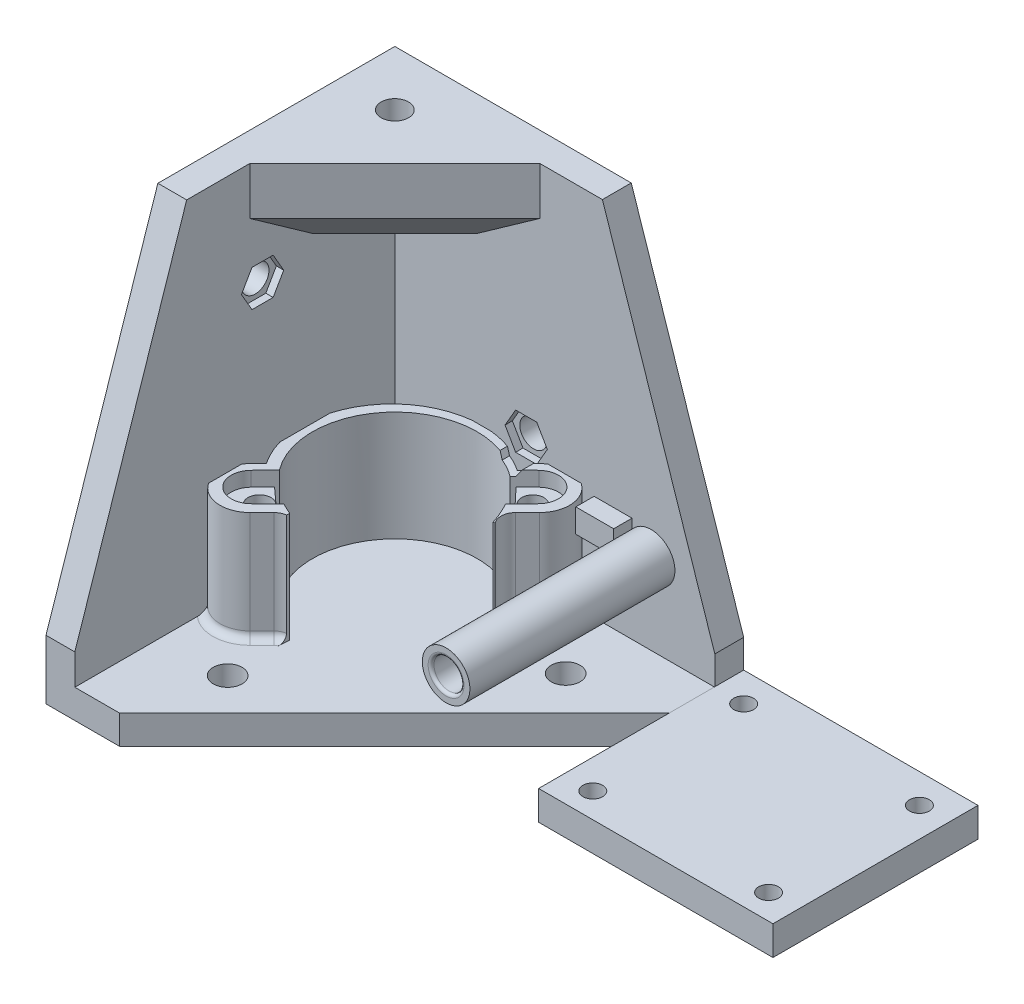
SolidWorks part; units mm, degrees
ref_plane "Front" through (0, 0, 0) normal (0, 0, 1) x (1, 0, 0)
ref_plane "Top" through (0, 0, 0) normal (0, 1, 0) x (1, 0, 0)
ref_plane "Right" through (0, 0, 0) normal (1, 0, 0) x (0, 0, -1)
sketch "Sketch1" plane through (0, 0, 0) normal (0, 1, 0) x (1, 0, 0)
  line L0 (0, 0) -> (0, 60.5)
  line L1 (0, -55) -> (0, 55) construction
  line L2 (0, 60.5) -> (60.5, 60.5)
  line L3 (60.5, 60.5) -> (60.5, 47.75)
  line L4 (60.5, 47.75) -> (12.75, 0)
  line L5 (-55, 0) -> (55, 0) construction
  line L6 (12.75, 0) -> (0, 0)
  dimension "D1" = 60.5
  dimension "D2" = 12.75
extrude "Boss-Extrude1" add sketch "Sketch1" along normal blind 5
sketch "Sketch4" plane through (0, 0, 0) normal (-1, 0, 0) x (0, 0, 1)
  line L0 (-60.5, 5) -> (-60.5, 68.5)
  line L1 (-60.5, 68.5) -> (-19.4, 68.5)
  line L2 (-19.4, 68.5) -> (0, 10.3086)
  line L3 (0, 10.3086) -> (0, 5)
  line L4 (0, -2.75) -> (0, 2.75) construction
  line L5 (-60.5, 5) -> (0, 5) construction
  line L6 (-60.5, 5) -> (0, 5)
  dimension "D1" = 63.5
  dimension "D2" = 41.1
  dimension "D3" = 61.34
extrude "Boss-Extrude2" add sketch "Sketch4" against normal blind 5
sketch "Sketch5" plane through (0, 0, -60.5) normal (0, 0, -1) x (-1, 0, 0)
  line L0 (0, 68.5) -> (-41, 68.5)
  line L1 (-41, 68.5) -> (-60.5, 10.0047)
  line L2 (-60.5, 10.0047) -> (-60.5, 5)
  line L6 (-60.5, 0) -> (0, 0)
  line L7 (0, 0) -> (0, 68.5)
  line L8 (0, 68.5) -> (-5, 68.5)
  line L9 (-5, 68.5) -> (-5, 5)
  line L10 (-5, 5) -> (-60.5, 5)
  line L11 (-60.5, 5) -> (-60.5, 0)
  line L12 (-60.5, 0) -> (0, 0)
  line L13 (0, 0) -> (0, 68.5)
  line L14 (0, 68.5) -> (-5, 68.5)
  line L15 (-5, 68.5) -> (-5, 5)
  line L16 (-5, 5) -> (-60.5, 5)
  line L17 (-60.5, 5) -> (-60.5, 0)
  line M13 (-5, 68.5) -> (-5, 5)
  line M14 (-5, 5) -> (-60.5, 5)
  dimension "D2" = 41
  dimension "D3" = 61.66
  dimension "D1" = 0
extrude "Boss-Extrude3" add sketch "Sketch5" against normal blind 5 contours L1 L2 L0 M14 M13 region at (28.6471, 34.3845, -60.5)
sketch "Sketch6" plane through (0, 5, 0) normal (0, 1, 0) x (1, 0, 0)
  line L0 (60.5, 60.5) -> (0, 60.5) construction
  line L4 (0, 19.4) -> (0, 0)
  line L5 (60.5, 55.5) -> (5, 55.5)
  line L6 (5, 55.5) -> (5, 0)
  line L7 (5, 0) -> (12.75, 0)
  line L8 (12.75, 0) -> (60.5, 47.75)
  line L9 (60.5, 47.75) -> (60.5, 55.5)
  line L10 (60.5, 55.5) -> (5, 55.5)
  line L11 (5, 55.5) -> (5, 0)
  line L12 (5, 0) -> (12.75, 0)
  line L13 (12.75, 0) -> (60.5, 47.75)
  line L14 (60.5, 47.75) -> (60.5, 55.5)
  line L15 (0, 0) -> (5, 0)
  line L16 (5, 0) -> (5, 19.4)
  line L17 (5, 19.4) -> (0, 19.4)
  line L18 (0, 19.4) -> (0, 0)
  line L19 (0, 0) -> (5, 0)
  line L20 (5, 0) -> (5, 19.4)
  line L21 (5, 19.4) -> (0, 19.4)
  line L24 (0, 60.5) -> (0, 19.4)
  line L25 (0, 19.4) -> (5, 19.4)
  line L26 (5, 19.4) -> (5, 55.5)
  line L27 (5, 55.5) -> (41, 55.5)
  line L28 (41, 55.5) -> (41, 60.5)
  line L29 (41, 60.5) -> (0, 60.5)
  line L30 (0, 60.5) -> (0, 19.4)
  line L31 (0, 19.4) -> (5, 19.4)
  line L32 (5, 19.4) -> (5, 55.5)
  line L33 (5, 55.5) -> (41, 55.5)
  line L34 (41, 55.5) -> (41, 60.5)
  line L35 (41, 60.5) -> (0, 60.5)
  circle A0 centre (16.5, 15) radius 2.5
  circle A1 centre (45.5, 44.625) radius 2.5
  dimension "D1" = 5
  dimension "D2" = 5
  dimension "D3" = 0
  dimension "D4" = 15
  dimension "D6" = 16.5
  dimension "D7" = 15
  dimension "D9" = 15.875
  dimension "D5" = 0
  dimension "D8" = 0
extrude "Cut-Extrude1" cut sketch "Sketch6" against normal through all contours A0 | A1 region at (16.5, 5, -15) region at (45.5, 5, -44.625)
sketch "Sketch9" plane through (0, 0, -55.5) normal (0, 0, 1) x (1, 0, 0)
  line L1 (5, 68.5) -> (5, 5) construction
  line L5 (0, 0) -> (60.5, 0)
  line L6 (0, 68.5) -> (0, 0)
  line L7 (41, 68.5) -> (0, 68.5)
  line L8 (60.5, 10.0047) -> (41, 68.5)
  line L9 (60.5, 0) -> (60.5, 10.0047)
  line L10 (0, 0) -> (60.5, 0)
  line L11 (0, 68.5) -> (0, 0)
  line L12 (41, 68.5) -> (0, 68.5)
  line L13 (60.5, 10.0047) -> (41, 68.5)
  line L14 (60.5, 0) -> (60.5, 10.0047)
  line L15 (49.45, 19.0462) -> (49.45, 11.3161) construction
  circle A0 centre (49.45, 19.0462) radius 4.1275
  circle A1 centre (49.45, 19.0462) radius 2.6035
  dimension "D2" = 5.207
  dimension "D3" = 1.524
  dimension "D4" = 49.4538
  dimension "D5" = 44.45
  dimension "D1" = 0
extrude "Boss-Extrude5" add sketch "Sketch9" along normal blind 35.56 contours A1 A0 region at (45.4392, 19.0462, -55.5)
fillet "Fillet1" radius 0.508 1 edges at (52.0535, 19.0462, -19.94)
sketch "Sketch14" plane through (0, 5, 0) normal (0, 1, 0) x (1, 0, 0)
  line L0 (13.4627, 27.5396) -> (14.7681, 26.7924)
  line L1 (12.75, 0) -> (60.5, 47.75) construction
  line L2 (36.625, 23.875) -> (5, 55.5) construction
  line L3 (5, 55.5) -> (60.5, 55.5) construction
  line L4 (32.9604, 47.0373) -> (33.7076, 45.7319)
  line L5 (14.8281, 26.8523) -> (11.8274, 23.8516)
  line L6 (6.723, 28.8027) -> (9.1327, 31.3641)
  line L7 (33.6477, 45.6719) -> (36.6484, 48.6726)
  line L8 (31.6973, 53.777) -> (29.1359, 51.3673)
  line L9 (15.0744, 24.4582) -> (13.006, 22.3898)
  line L10 (5.6561, 29.7396) -> (7.0609, 31.1444)
  line L11 (36.0418, 45.4256) -> (38.1102, 47.494)
  line L12 (30.7604, 54.8439) -> (28.83, 52.9135)
  line L13 (18.1324, 24.8665) -> (30.5234, 17.7734)
  line L14 (35.6335, 42.3676) -> (42.7266, 29.9766)
  line L15 (31.7409, 18.9909) -> (18.852, 25.7543)
  line L16 (41.5091, 28.7591) -> (34.7457, 41.648)
  line L17 (16.5689, 25.6946) -> (16.5343, 25.1798)
  line L18 (34.7457, 41.648) -> (35.7996, 42.0774)
  circle A0 centre (20.5607, 39.9393) radius 14.2875
  arc A1 (11.8274, 23.8516) -> (6.723, 28.8027) centre (9.3129, 26.3661) cw
  arc A2 (36.6484, 48.6726) -> (31.6973, 53.777) centre (34.1339, 51.1871) ccw
  arc A3 (13.006, 22.3898) -> (5.6561, 29.7396) centre (9.3311, 26.0647) cw
  arc A4 (38.1102, 47.494) -> (30.7604, 54.8439) centre (34.4353, 51.1689) ccw
  arc A5 (7.0609, 31.1444) -> (28.83, 52.9135) centre (20.0709, 39.9035) cw
  arc A6 (36.0418, 45.4256) -> (35.6335, 42.3676) centre (37.8378, 43.6295) ccw
  arc A7 (15.0744, 24.4582) -> (18.1324, 24.8665) centre (16.8705, 22.6622) cw
  arc A9 (33.8602, 45.8844) -> (36.3595, 38.5726) centre (13.6025, 34.877) cw
  arc A10 (14.6156, 26.6398) -> (21.9274, 24.1405) centre (25.623, 46.8975) ccw
  point P40 (34.6689, 44.0527)
  point P43 (16.4473, 25.8311)
  line M13 (60.5, 55.5) -> (5, 55.5)
  line M14 (5, 55.5) -> (5, 0)
  line M16 (12.75, 0) -> (60.5, 47.75)
  dimension "D1" = 28.575
  dimension "D2" = 3.556
  dimension "D3" = 2.54
extrude "Boss-Extrude6" add sketch "Sketch14" along normal blind 19.05 contours L2 A0 L5 A1 L6 A5 L10 A3 L9 A7 L13 M16 M14 | L2 L14 A6 L11 A4 L12 A5 A0 L8 A2 L7 M16 M13 region at (7.691, 5, -30.3062) region at (10.0875, 5, -50.8829)
sketch "Sketch15" plane through (0, 68.5, 0) normal (0, 1, 0) x (1, 0, 0)
  line L0 (5, 30.3375) -> (30.1625, 55.5)
  line L1 (0, -33.275) -> (0, 33.275) construction
  line L2 (41, 60.5) -> (0, 60.5) construction
  line L6 (0, 60.5) -> (0, 19.4)
  line L7 (0, 19.4) -> (5, 19.4)
  line L8 (5, 19.4) -> (5, 55.5)
  line L9 (5, 55.5) -> (41, 55.5)
  line L10 (41, 55.5) -> (41, 60.5)
  line L11 (41, 60.5) -> (0, 60.5)
  line L13 (0, 19.4) -> (5, 19.4)
  line L14 (5, 30.3375) -> (5, 55.5)
  line L15 (5, 55.5) -> (30.1625, 55.5)
  line L16 (41, 55.5) -> (41, 60.5)
  circle A0 centre (9.525, 50.975) radius 2.3812
  line M11 (5, 19.4) -> (5, 55.5)
  line M12 (5, 55.5) -> (41, 55.5)
  dimension "D3" = 4.7625
  dimension "D4" = 9.525
  dimension "D5" = 9.525
  dimension "D2" = 45
  dimension "D1" = 0
extrude "Boss-Extrude7" add sketch "Sketch15" against normal blind 15.875 contours L0 A0 M11 M12 region at (13.6178, 68.5, -46.8822)
chamfer "Chamfer2" distance 7.62 angle 45 1 edges at (17.5813, 52.625, -42.9187)
fillet "Fillet2" radius 1.27 7 edges at (39.6065, 5, -51.6871) (37.076, 5, -46.4598) (35.3202, 5, -43.9657) (8.8129, 5, -20.8935) (14.0402, 5, -23.424) (15.745, 5, -24.9392) (35.7165, 5, -42.2225)
sketch "Sketch16" plane through (0, 0, -55.5) normal (0, 0, 1) x (1, 0, 0)
  line L1 (46.1305, 23.2107) -> (38.2864, 23.2107)
  line L2 (46.1305, 23.2107) -> (46.1305, 19.0978)
  line L3 (46.1305, 19.0978) -> (38.2864, 19.0978)
  line L4 (38.2864, 23.2107) -> (38.2864, 19.0978)
extrude "Boss-Extrude8" add sketch "Sketch16" along normal blind 3.175
chamfer "Chamfer3" distance 1.27 angle 45 1 edges at (38.2864, 23.2107, -55.0794)
sketch "Sketch17" plane through (0, 5, 0) normal (0, 1, 0) x (1, 0, 0)
  line L0 (8.716, 30.9212) -> (14.047, 26.0712)
  line L1 (36.625, 23.875) -> (5, 55.5) construction
  line L2 (12.75, 0) -> (60.5, 47.75) construction
  line L3 (5, 55.5) -> (18.418, 55.5) construction
  line L4 (5, 55.5) -> (5, 44.2452) construction
  line L5 (29.6632, 51.8634) -> (34.5959, 46.6202)
  line L22 (37.3079, 55.5) -> (31.5627, 55.5)
  line L23 (30.7604, 54.8439) -> (28.83, 52.9135)
  line L24 (21.7238, 55.5) -> (18.418, 55.5)
  line L25 (5, 44.2452) -> (5, 35.5618)
  line L26 (7.0609, 31.1444) -> (5.6561, 29.7396)
  line L27 (5, 28.9373) -> (5, 23.1921)
  line L28 (13.006, 22.3898) -> (15.0744, 24.4582)
  line L29 (16.5343, 25.1798) -> (16.5689, 25.6946)
  line L30 (16.5343, 25.1798) -> (16.5689, 25.6946)
  line L31 (35.539, 41.9712) -> (35.7996, 42.0774)
  line L32 (35.539, 41.9712) -> (35.7996, 42.0774)
  line L33 (14.6156, 26.6398) -> (11.8274, 23.8516)
  line L34 (6.723, 28.8027) -> (9.1327, 31.3641)
  line L35 (29.1359, 51.3673) -> (31.6973, 53.777)
  line L36 (36.6484, 48.6726) -> (33.8602, 45.8844)
  line L40 (35.7996, 42.0774) -> (35.6335, 42.3676)
  line L41 (36.0418, 45.4256) -> (38.1102, 47.494)
  line L43 (37.3079, 55.5) -> (31.5627, 55.5)
  line L44 (30.7604, 54.8439) -> (28.83, 52.9135)
  line L45 (21.7238, 55.5) -> (18.418, 55.5)
  line L46 (5, 44.2452) -> (5, 35.5618)
  line L47 (7.0609, 31.1444) -> (5.6561, 29.7396)
  line L48 (5, 28.9373) -> (5, 23.1921)
  line L49 (13.006, 22.3898) -> (15.0744, 24.4582)
  line L54 (14.6156, 26.6398) -> (11.8274, 23.8516)
  line L55 (6.723, 28.8027) -> (9.1327, 31.3641)
  line L56 (29.1359, 51.3673) -> (31.6973, 53.777)
  line L57 (36.6484, 48.6726) -> (33.8602, 45.8844)
  line L61 (35.7996, 42.0774) -> (35.6335, 42.3676)
  line L62 (36.0418, 45.4256) -> (38.1102, 47.494)
  circle A1 centre (33.6908, 50.7324) radius 2.1828
  circle A2 centre (10.0204, 27.0078) radius 1.9844
  circle A3 centre (33.6908, 50.7324) radius 1.9288
  arc A15 (38.1102, 47.494) -> (37.3079, 55.5) centre (34.4353, 51.1689) ccw
  arc A17 (31.5627, 55.5) -> (30.7604, 54.8439) centre (34.4353, 51.1689) ccw
  arc A18 (28.83, 52.9135) -> (21.7238, 55.5) centre (20.0709, 39.9035) ccw
  arc A19 (18.418, 55.5) -> (5, 44.2452) centre (20.0709, 39.9035) ccw
  arc A20 (5, 35.5618) -> (7.0609, 31.1444) centre (20.0709, 39.9035) ccw
  arc A21 (5.6561, 29.7396) -> (5, 28.9373) centre (9.3311, 26.0647) ccw
  arc A22 (5, 23.1921) -> (13.006, 22.3898) centre (9.3311, 26.0647) ccw
  arc A23 (16.5343, 25.1798) -> (15.0744, 24.4582) centre (16.8705, 22.6622) ccw
  arc A24 (14.6156, 26.6398) -> (16.5689, 25.6946) centre (25.623, 46.8975) ccw
  arc A25 (6.723, 28.8027) -> (11.8274, 23.8516) centre (9.3129, 26.3661) ccw
  arc A26 (29.1359, 51.3673) -> (9.1327, 31.3641) centre (20.5607, 39.9393) ccw
  arc A27 (36.6484, 48.6726) -> (31.6973, 53.777) centre (34.1339, 51.1871) ccw
  arc A28 (35.539, 41.9712) -> (33.8602, 45.8844) centre (13.6025, 34.877) ccw
  arc A29 (36.0418, 45.4256) -> (35.6335, 42.3676) centre (37.8378, 43.6295) ccw
  arc A30 (38.1102, 47.494) -> (37.3079, 55.5) centre (34.4353, 51.1689) ccw
  arc A32 (31.5627, 55.5) -> (30.7604, 54.8439) centre (34.4353, 51.1689) ccw
  arc A33 (28.83, 52.9135) -> (21.7238, 55.5) centre (20.0709, 39.9035) ccw
  arc A34 (18.418, 55.5) -> (5, 44.2452) centre (20.0709, 39.9035) ccw
  arc A35 (5, 35.5618) -> (7.0609, 31.1444) centre (20.0709, 39.9035) ccw
  arc A36 (5.6561, 29.7396) -> (5, 28.9373) centre (9.3311, 26.0647) ccw
  arc A37 (5, 23.1921) -> (13.006, 22.3898) centre (9.3311, 26.0647) ccw
  arc A38 (16.5343, 25.1798) -> (15.0744, 24.4582) centre (16.8705, 22.6622) ccw
  arc A39 (14.6156, 26.6398) -> (16.5689, 25.6946) centre (25.623, 46.8975) ccw
  arc A40 (6.723, 28.8027) -> (11.8274, 23.8516) centre (9.3129, 26.3661) ccw
  arc A41 (29.1359, 51.3673) -> (9.1327, 31.3641) centre (20.5607, 39.9393) ccw
  arc A42 (36.6484, 48.6726) -> (31.6973, 53.777) centre (34.1339, 51.1871) ccw
  arc A43 (35.539, 41.9712) -> (33.8602, 45.8844) centre (13.6025, 34.877) ccw
  arc A44 (36.0418, 45.4256) -> (35.6335, 42.3676) centre (37.8378, 43.6295) ccw
  line M44 (33.8602, 45.8844) -> (36.6484, 48.6726)
  arc M45 (36.6484, 48.6726) -> (31.6973, 53.777) centre (34.1339, 51.1871) ccw
  line M46 (31.6973, 53.777) -> (29.1359, 51.3673)
  line M48 (9.1327, 31.3641) -> (6.723, 28.8027)
  arc M49 (6.723, 28.8027) -> (11.8274, 23.8516) centre (9.3129, 26.3661) ccw
  line M50 (11.8274, 23.8516) -> (14.6156, 26.6398)
  dimension "D2" = 3.9688
  dimension "D3" = 0.254
  dimension "D1" = 0
extrude "Boss-Extrude9" add sketch "Sketch17" along normal offset from surface (16.51 mm away) 2.54 contours L5 A1 M46 M44 M45 | L0 M48 M49 M50 | A1 L5 A3 region at (11.3737, 5, -28.4876) region at (30.7585, 5, -52.737) region at (33.0584, 5, -52.7569) up to face at (20.9693, 24.05, -39.9839)
sketch "Sketch18" plane through (0, 0, 0) normal (-1, 0, 0) x (0, 0, 1)
  line L0 (-60.5, 68.5) -> (-60.5, 0) construction
  line L1 (33.275, 0) -> (-33.275, 0) construction
  circle A0 centre (-32.56, 49.53) radius 2.3813
  dimension "D1" = 27.94
  dimension "D2" = 49.53
  dimension "D3" = 4.7625
extrude "Cut-Extrude2" cut sketch "Sketch18" against normal up to next
sketch "Sketch19" plane through (0, 0, -60.5) normal (0, 0, -1) x (-1, 0, 0)
  line L0 (0, 33.275) -> (0, -33.275) construction
  line L1 (33.275, 0) -> (-33.275, 0) construction
  circle A0 centre (-27.7812, 26.1937) radius 2.3813
  dimension "D1" = 27.7812
  dimension "D2" = 26.1937
  dimension "D3" = 4.7625
extrude "Cut-Extrude3" cut sketch "Sketch19" against normal up to next
sketch "Sketch20" plane through (0, 0, -55.5) normal (0, 0, 1) x (1, 0, 0)
  line L1 (31.4474, 26.1937) -> (29.6143, 29.3687)
  line L2 (29.6143, 29.3687) -> (25.9482, 29.3687)
  line L3 (25.9482, 29.3687) -> (24.1151, 26.1937)
  line L4 (24.1151, 26.1937) -> (25.9482, 23.0187)
  line L5 (25.9482, 23.0187) -> (29.6143, 23.0187)
  line L6 (29.6143, 23.0187) -> (31.4474, 26.1937)
  circle A0 centre (27.7812, 26.1937) radius 2.3813 construction
  circle A1 centre (27.7812, 26.1937) radius 2.3813
  circle A2 centre (27.7812, 26.1937) radius 3.175 construction
  dimension "D1" = 6.35
extrude "Cut-Extrude4" cut sketch "Sketch20" against normal blind 1.27 and the other way up to vertex (4.1327 mm away) contours L1 L2 L3 L4 L5 L6 other way up to point (29.1359, 24.05, -51.3673)
sketch "Sketch21" plane through (5, 0, 0) normal (1, 0, 0) x (0, 0, -1)
  line L1 (34.3931, 52.705) -> (30.7269, 52.705)
  line L2 (30.7269, 52.705) -> (28.8938, 49.53)
  line L3 (28.8938, 49.53) -> (30.7269, 46.355)
  line L4 (30.7269, 46.355) -> (34.3931, 46.355)
  line L5 (34.3931, 46.355) -> (36.2262, 49.53)
  line L6 (36.2262, 49.53) -> (34.3931, 52.705)
  circle A0 centre (32.56, 49.53) radius 2.3813 construction
  circle A1 centre (32.56, 49.53) radius 2.3812
  circle A2 centre (32.56, 49.53) radius 3.175 construction
  dimension "D1" = 6.35
extrude "Cut-Extrude5" cut sketch "Sketch21" against normal blind 1.27 contours L1 L2 L3 L4 L5 L6
sketch "Sketch23" plane through (0, 0, 0) normal (0, 1, 0) x (1, 0, 0)
  line L1 (60.5, 60.5) -> (101.14, 60.5)
  line L2 (60.5, 60.5) -> (60.5, 24.94)
  line L3 (60.5, 24.94) -> (101.14, 24.94)
  line L4 (101.14, 60.5) -> (101.14, 24.94)
  dimension "D1" = 40.64
  dimension "D2" = 35.56
extrude "Boss-Extrude12" add sketch "Sketch23" along normal blind 5.08
sketch "Sketch24" plane through (0, 5.08, 0) normal (0, 1, 0) x (1, 0, 0)
  line L0 (101.14, 60.5) -> (60.5, 60.5) construction
  line L1 (60.5, 47.75) -> (60.5, 55.5) construction
  circle A0 centre (65.58, 55.42) radius 1.7145
  circle A1 centre (96.06, 55.42) radius 1.7145
  circle A2 centre (96.06, 29.258) radius 1.7145
  circle A3 centre (65.58, 29.258) radius 1.7145
  dimension "D1" = 3.429
  dimension "D2" = 26.162
  dimension "D3" = 30.48
  dimension "D4" = 5.08
  dimension "D5" = 5.08
extrude "Cut-Extrude6" cut sketch "Sketch24" against normal up to next
